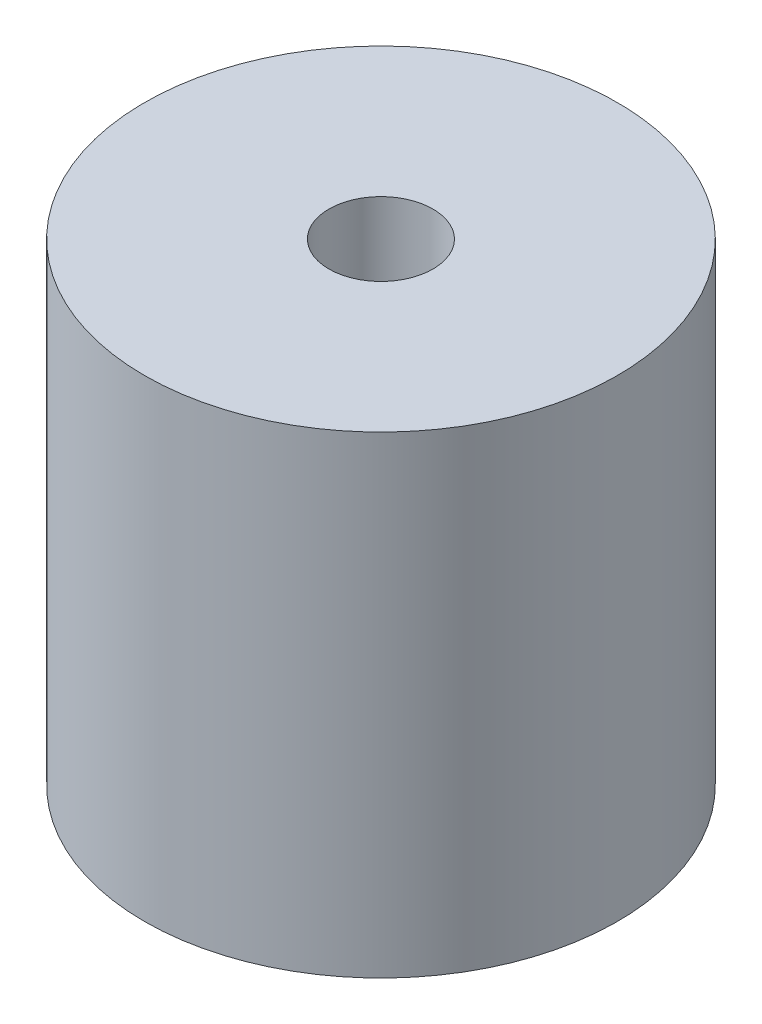
SolidWorks part; units mm, degrees
material "橡胶"
ref_plane "前视基准面" through (0, 0, 0) normal (0, 0, 1) x (1, 0, 0)
ref_plane "上视基准面" through (0, 0, 0) normal (0, 1, 0) x (1, 0, 0)
ref_plane "右视基准面" through (0, 0, 0) normal (1, 0, 0) x (0, 0, -1)
sketch "草图1" plane through (0, 0, 0) normal (0, 1, 0) x (1, 0, 0)
  circle A0 centre (0, 0) radius 7.5
  dimension "D1" = 15
extrude "凸台-拉伸1" add sketch "草图1" along normal mid plane 15
hole_wizard "M4 螺纹孔1" positions "草图3" profile "草图2" tap size "M4" standard "GB" end condition through all
sketch "草图3" plane through (0, 7.5, 0) normal (0, 1, 0) x (1, 0, 0)
  point P0 (0, 0)
cosmetic thread "孔螺蚊线1" parameters "D2"=4
sketch "草图2" plane through (0, 7.5, 0) normal (1, 0, 0) x (0, 0, 1)
  line L0 (0, 0) -> (0, 15)
  line L1 (0, 15) -> (1.65, 15)
  line L2 (1.65, 15) -> (1.65, 0)
  line L5 (1.65, 0) -> (0, 0)
  line L11 (0, -6.35) -> (0, 107.95) construction
  dimension "通孔螺纹孔钻头直径" = 3.3
  dimension "通孔螺纹孔钻头深度" = 15
sketch "草图4" plane through (0, -7.5, 0) normal (0, -1, 0) x (1, 0, 0)
  circle A0 centre (0, 0) radius 2
  dimension "D1" = 4
extrude "凸台-拉伸2" [suppressed] add sketch "草图4" along normal blind 10
move or copy body "实体-移动/复制1" [suppressed] bodies to move or copy 107
